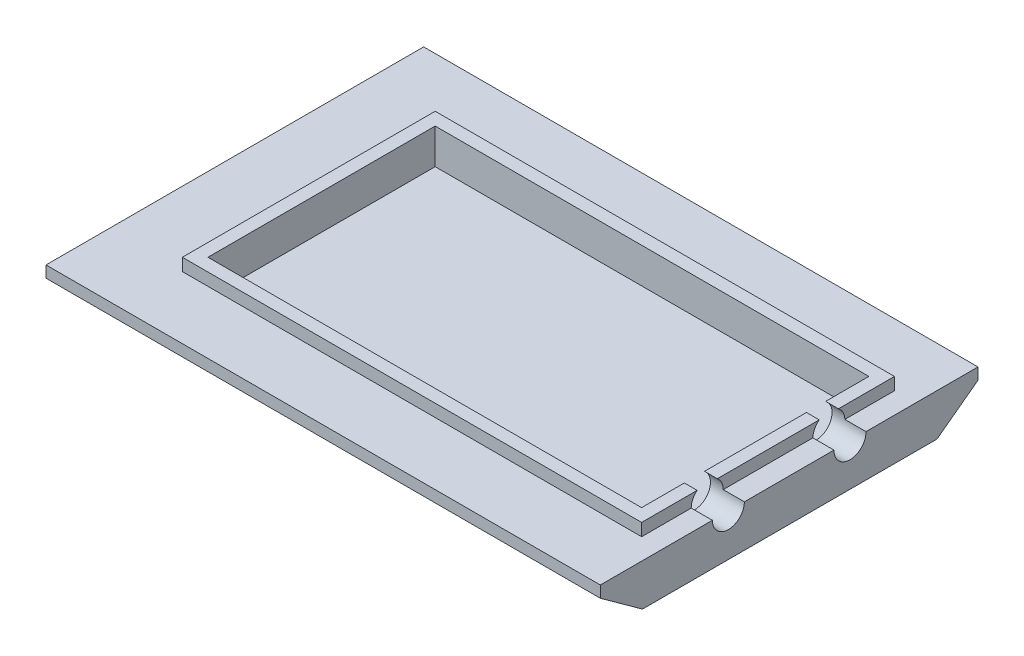
SolidWorks part; units mm, degrees
ref_plane "Front Plane" through (0, 0, 0) normal (0, 0, 1) x (1, 0, 0)
ref_plane "Top Plane" through (0, 0, 0) normal (0, 1, 0) x (1, 0, 0)
ref_plane "Right Plane" through (0, 0, 0) normal (1, 0, 0) x (0, 0, -1)
sketch "Sketch1" plane through (0, 0, 0) normal (0, 1, 0) x (1, 0, 0)
  line L1 (-190.5, 0) -> (0, 0)
  line L2 (-190.5, 0) -> (-190.5, -116.84)
  line L3 (-190.5, -116.84) -> (0, -116.84)
  line L4 (0, 0) -> (0, -116.84)
  dimension "D1" = 190.5
  dimension "D2" = 116.84
ref_plane "Plane1" through (0, 12.0904, 0) normal (0, 1, 0) x (1, 0, 0)
sketch "Sketch2" plane through (0, 12.0904, 0) normal (0, 1, 0) x (1, 0, 0)
  line L0 (0, -6.6497) -> (0, 6.6497) construction
  line L1 (-219.964, 16.2891) -> (0, 16.2891)
  line L2 (-219.964, 16.2891) -> (-219.964, -133.5709)
  line L3 (-219.964, -133.5709) -> (0, -133.5709)
  line L4 (0, 16.2891) -> (0, -133.5709)
  line L5 (-190.5, 0) -> (0, 0) construction
  dimension "D1" = 149.86
  dimension "D2" = 219.964
  dimension "D3" = 16.2891
loft "Loft1" add profiles "Sketch2", "Sketch1" connector at (-219.964, 12.0904, 133.5709) connector at (-190.5, 0, 116.84)
extrude "Boss-Extrude2" add sketch "Sketch2<2>" along normal blind 4.572
sketch "Sketch2<2>" plane through (0, 12.0904, 0) normal (0, 1, 0) x (1, 0, 0) same geometry as "Sketch2"
ref_plane "Plane2" through (0, 16.51, 0) normal (0, 1, 0) x (1, 0, 0)
sketch "Sketch3" plane through (0, 16.51, 0) normal (0, 1, 0) x (1, 0, 0)
  line L0 (0, -133.5709) -> (0, 16.2891) construction
  line L1 (-190.627, -8.4759) -> (-8.382, -8.4759)
  line L2 (-190.627, -8.4759) -> (-190.627, -108.8059)
  line L3 (-190.627, -108.8059) -> (-8.382, -108.8059)
  line L4 (-8.382, -8.4759) -> (-8.382, -108.8059)
  line L5 (-219.964, -133.5709) -> (0, -133.5709) construction
  dimension "D1" = 182.245
  dimension "D2" = 100.33
  dimension "D3" = 8.382
  dimension "D4" = 24.765
extrude "Boss-Extrude3" add sketch "Sketch3" along normal blind 5.08
sketch "Sketch4" plane through (0, 16.51, 0) normal (0, 1, 0) x (1, 0, 0)
  line L0 (-185.547, -13.5559) -> (-185.547, -103.7259)
  line L5 (-185.547, -103.7259) -> (-13.462, -103.7259)
  line L6 (-13.462, -13.5559) -> (-13.462, -103.7259)
  line L7 (-185.547, -13.5559) -> (-13.462, -13.5559)
  line L8 (-8.382, -108.8059) -> (-8.382, -8.4759) construction
  line L9 (-190.627, -8.4759) -> (-190.627, -108.8059) construction
  line L11 (-190.627, -8.4759) -> (-8.382, -8.4759) construction
  line L12 (-190.627, -108.8059) -> (-8.382, -108.8059) construction
  dimension "D1" = 5.08
  dimension "D2" = 5.08
  dimension "D3" = 5.08
  dimension "D4" = 5.08
extrude "Cut-Extrude1" cut sketch "Sketch4" along normal through all
extrude "Cut-Extrude2" cut sketch "Sketch4<2>" against normal blind 8.89
sketch "Sketch4<2>" plane through (0, 16.51, 0) normal (0, 1, 0) x (1, 0, 0) same geometry as "Sketch4"
sketch "Sketch5" plane through (0, 0, 0) normal (1, 0, 0) x (0, 0, -1)
  line L0 (-133.5709, 16.6624) -> (16.2891, 16.6624) construction
  line L1 (82.4231, 16.51) -> (-82.4231, 16.51) construction
  circle A0 centre (-82.7709, 16.6624) radius 6.35
  circle A1 centre (-34.5109, 16.51) radius 6.35
  dimension "D1" = 12.7
  dimension "D3" = 12.7
  dimension "D2" = 50.8
  dimension "D4" = 50.8
extrude "Cut-Extrude3" cut sketch "Sketch5" against normal blind 19.05
